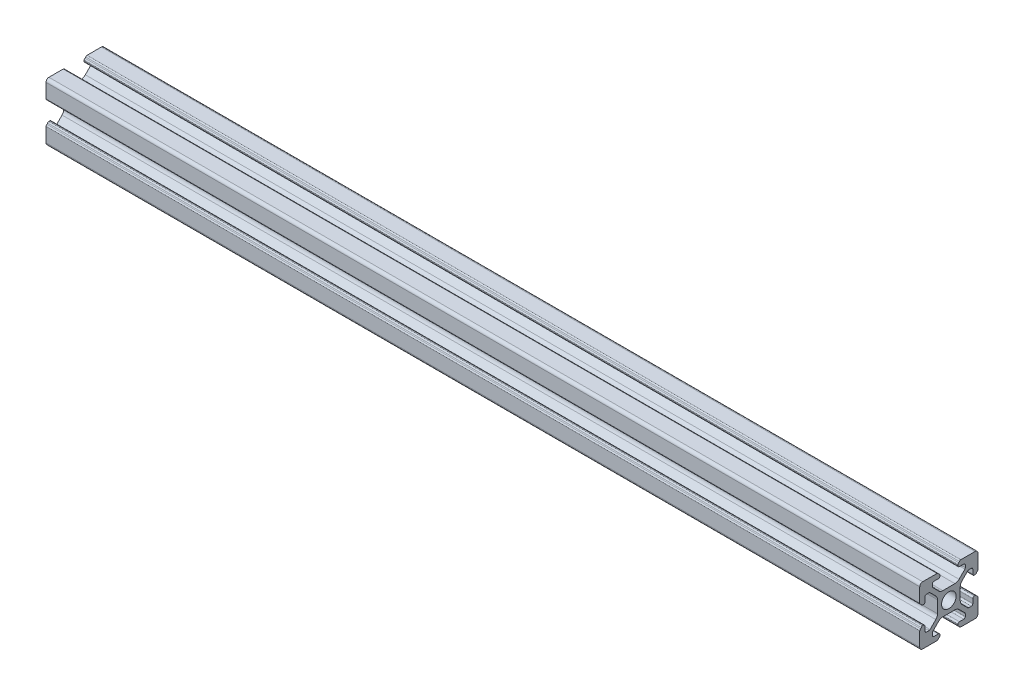
SolidWorks part; units mm, degrees
ref_plane "Front Plane" through (0, 0, 0) normal (0, 0, 1) x (1, 0, 0)
ref_plane "Top Plane" through (0, 0, 0) normal (0, 1, 0) x (1, 0, 0)
ref_plane "Right Plane" through (0, 0, 0) normal (1, 0, 0) x (0, 0, -1)
sketch "Sketch1" plane through (0, 0, 0) normal (1, 0, 0) x (0, 0, -1)
  line L0 (10, 10) -> (-10, -10) construction
  line L1 (-10, 10) -> (10, 10)
  line L2 (-10, 10) -> (-10, -10)
  line L3 (-10, -10) -> (10, -10)
  line L4 (10, 10) -> (10, -10)
  dimension "D1" = 20
extrude "Boss-Extrude1" add sketch "Sketch1" along normal blind 300
fillet "Fillet1" radius 1 4 edges at (150, -10, -10) (150, -10, 10) (150, 10, -10) (150, 10, 10)
sketch "Sketch3" plane through (0, 0, 0) normal (-1, 0, 0) x (0, 0, 1)
  line L0 (-3.6, 10) -> (3.6, 10)
  line L1 (-9, 10) -> (9, 10) construction
  line L2 (3.6, 10) -> (3.6, 9.5)
  line L3 (3.6, 9.5) -> (3.1, 9.5)
  line L4 (3.1, 9.5) -> (3.1, 8.2)
  line L5 (3.1, 8.2) -> (5.63, 8.2)
  line L6 (5.63, 8.2) -> (5.63, 6.6199)
  line L7 (5.63, 6.6199) -> (2.9101, 3.9)
  line L8 (2.9101, 3.9) -> (-2.9101, 3.9)
  line L9 (-2.9101, 3.9) -> (-5.63, 6.6199)
  line L10 (-5.63, 6.6199) -> (-5.63, 8.2)
  line L11 (-5.63, 8.2) -> (-3.1, 8.2)
  line L12 (-3.1, 8.2) -> (-3.1, 9.5)
  line L13 (-3.1, 9.5) -> (-3.6, 9.5)
  line L14 (-3.6, 9.5) -> (-3.6, 10)
  line L15 (0, 10) -> (0, 3.9) construction
  line L16 (10, 3.6) -> (10, -3.6)
  line L17 (10, -3.6) -> (9.5, -3.6)
  line L18 (9.5, -3.6) -> (9.5, -3.1)
  line L19 (9.5, -3.1) -> (8.2, -3.1)
  line L20 (8.2, -3.1) -> (8.2, -5.63)
  line L21 (8.2, -5.63) -> (6.6199, -5.63)
  line L22 (6.6199, -5.63) -> (3.9, -2.9101)
  line L23 (3.9, -2.9101) -> (3.9, 2.9101)
  line L24 (3.9, 2.9101) -> (6.6199, 5.63)
  line L25 (6.6199, 5.63) -> (8.2, 5.63)
  line L26 (8.2, 5.63) -> (8.2, 3.1)
  line L27 (8.2, 3.1) -> (9.5, 3.1)
  line L28 (9.5, 3.1) -> (9.5, 3.6)
  line L29 (9.5, 3.6) -> (10, 3.6)
  line L30 (10, 0) -> (3.9, 0) construction
  line L31 (3.6, -10) -> (-3.6, -10)
  line L32 (-3.6, -10) -> (-3.6, -9.5)
  line L33 (-3.6, -9.5) -> (-3.1, -9.5)
  line L34 (-3.1, -9.5) -> (-3.1, -8.2)
  line L35 (-3.1, -8.2) -> (-5.63, -8.2)
  line L36 (-5.63, -8.2) -> (-5.63, -6.6199)
  line L37 (-5.63, -6.6199) -> (-2.9101, -3.9)
  line L38 (-2.9101, -3.9) -> (2.9101, -3.9)
  line L39 (2.9101, -3.9) -> (5.63, -6.6199)
  line L40 (5.63, -6.6199) -> (5.63, -8.2)
  line L41 (5.63, -8.2) -> (3.1, -8.2)
  line L42 (3.1, -8.2) -> (3.1, -9.5)
  line L43 (3.1, -9.5) -> (3.6, -9.5)
  line L44 (3.6, -9.5) -> (3.6, -10)
  line L45 (0, -10) -> (0, -3.9) construction
  line L46 (-10, -3.6) -> (-10, 3.6)
  line L47 (-10, 3.6) -> (-9.5, 3.6)
  line L48 (-9.5, 3.6) -> (-9.5, 3.1)
  line L49 (-9.5, 3.1) -> (-8.2, 3.1)
  line L50 (-8.2, 3.1) -> (-8.2, 5.63)
  line L51 (-8.2, 5.63) -> (-6.6199, 5.63)
  line L52 (-6.6199, 5.63) -> (-3.9, 2.9101)
  line L53 (-3.9, 2.9101) -> (-3.9, -2.9101)
  line L54 (-3.9, -2.9101) -> (-6.6199, -5.63)
  line L55 (-6.6199, -5.63) -> (-8.2, -5.63)
  line L56 (-8.2, -5.63) -> (-8.2, -3.1)
  line L57 (-8.2, -3.1) -> (-9.5, -3.1)
  line L58 (-9.5, -3.1) -> (-9.5, -3.6)
  line L59 (-9.5, -3.6) -> (-10, -3.6)
  line L60 (-10, 0) -> (-3.9, 0) construction
  line L61 (10, 9) -> (10, -9) construction
  line L62 (-10, -9) -> (-10, 9) construction
  point P4 (0, 10)
  point P17 (0, 0)
  point P26 (10, 0)
  point P43 (0, -10)
  point P60 (-10, 0)
  point P75 (0, 0)
  dimension "D1" = 135
  dimension "D2" = 6.2
  dimension "D3" = 7.2
  dimension "D4" = 6.1
  dimension "D5" = 11.26
  dimension "D6" = 0.5
  dimension "D8" = 1.4
  dimension "D9" = 1.8
  dimension "D7" = 4
extrude "Cut-Extrude1" cut sketch "Sketch3" against normal through all
hole_wizard "Ø5.0 (5) Diameter Hole1" positions "Sketch4" profile "Sketch5" hole size "Ø5.0" standard "ANSI Metric" end condition through all
sketch "Sketch4" plane through (0, 0, 0) normal (-1, 0, 0) x (0, 0, 1)
  point P0 (0, 0)
sketch "Sketch5" plane through (0, 0, 0) normal (0, 1, 0) x (0, 0, 1)
  line L0 (0, 0) -> (0, 300)
  line L1 (0, 300) -> (2.5, 300)
  line L2 (2.5, 300) -> (2.5, 0)
  line L5 (2.5, 0) -> (0, 0)
  line L11 (0, -6.35) -> (0, 107.95) construction
  dimension "Thru Hole Dia." = 5
  dimension "Thru Hole Depth" = 300
fillet "Fillet2" radius 2 8 edges at (150, -3.9, -2.9101) (150, -3.9, 2.9101) (150, -2.9101, 3.9) (150, 2.9101, 3.9) (150, 3.9, 2.9101) (150, 3.9, -2.9101) (150, 2.9101, -3.9) (150, -2.9101, -3.9)
fillet "Fillet3" radius 0.5 20 edges at (150, 3.6, -10) (150, 3.1, -9.5) (150, 3.1, -8.2) (150, 5.63, -8.2) (150, 5.63, -6.6199) (150, 3.6, 10) (150, 3.1, 9.5) (150, 3.1, 8.2) (150, 5.63, 8.2) (150, 5.63, 6.6199) (150, 6.6199, 5.63) (150, 8.2, 5.63) (150, 8.2, 3.1) (150, 9.5, 3.1) (150, 10, 3.6) (150, 9.5, -3.1) (150, 10, -3.6) (150, 8.2, -3.1) (150, 8.2, -5.63) (150, 6.6199, -5.63)
fillet "Fillet4" radius 0.5 20 edges at (150, -3.6, 10) (150, -3.1, 9.5) (150, -3.1, 8.2) (150, -5.63, 8.2) (150, -5.63, 6.6199) (150, -6.6199, 5.63) (150, -8.2, 5.63) (150, -8.2, 3.1) (150, -10, 3.6) (150, -9.5, 3.1) (150, -10, -3.6) (150, -9.5, -3.1) (150, -8.2, -3.1) (150, -8.2, -5.63) (150, -6.6199, -5.63) (150, -5.63, -6.6199) (150, -5.63, -8.2) (150, -3.1, -8.2) (150, -3.1, -9.5) (150, -3.6, -10)
fillet "Fillet5" radius 0.5 8 edges at (150, 3.6, -9.5) (150, -3.6, -9.5) (150, -9.5, -3.6) (150, -9.5, 3.6) (150, -3.6, 9.5) (150, 3.6, 9.5) (150, 9.5, 3.6) (150, 9.5, -3.6)
